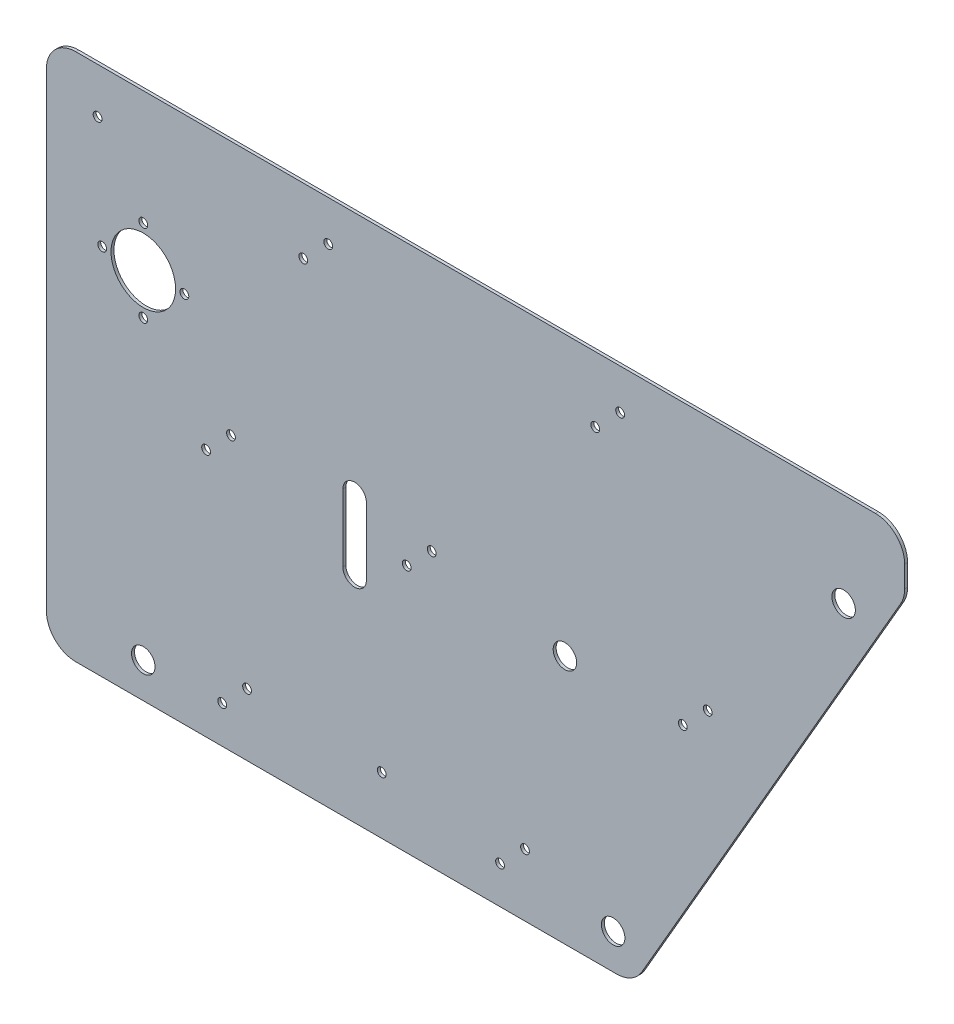
SolidWorks part; units mm, degrees
ref_plane "Front Plane" through (0, 0, 0) normal (0, 0, 1) x (1, 0, 0)
ref_plane "Top Plane" through (0, 0, 0) normal (0, 1, 0) x (1, 0, 0)
ref_plane "Right Plane" through (0, 0, 0) normal (1, 0, 0) x (0, 0, -1)
sketch "Sketch1" plane through (0, 0, 0) normal (0, 0, 1) x (1, 0, 0)
  line L0 (100, 80) -> (192.376, 80)
  line L1 (-100, -80) -> (100, -80)
  line L2 (-100, -80) -> (-100, 80)
  line L3 (-100, 80) -> (100, 80)
  line L4 (100, -80) -> (100, 80)
  line L5 (-100, -80) -> (100, 80) construction
  line L6 (-100, 80) -> (100, -80) construction
  line L7 (192.376, 80) -> (100, -80)
  line L8 (100, 80) -> (100, -80)
  line L10 (-100, 80) -> (192.376, 80)
  line L11 (-100, 80) -> (-100, 100)
  line L12 (-100, 100) -> (192.376, 100)
  line L13 (192.376, 80) -> (192.376, 100)
  point P0 (0, 0)
  dimension "D1" = 160
  dimension "D2" = 200
  dimension "D3" = 30
  dimension "D4" = 20
extrude "Boss-Extrude1" add sketch "Sketch1" along normal blind 1 contours L1 L4 L3 L2 | L7 L0 L4 | L11 L10 L13 L12 region at (0, 0, 0) region at (130.792, 26.6667, 0)
fillet "Fillet1" radius 10 5 edges at (100, -80, 0.5) (-100, -80, 0.5) (192.376, 100, 0.5) (192.376, 80, 0.5) (-100, 100, 0.5)
sketch "Sketch2" plane through (0, 0, 1) normal (0, 0, 1) x (1, 0, 0)
  line L0 (-90, -80) -> (94.2265, -80) construction
  line L1 (191.0363, 77.6795) -> (102.8868, -75) construction
  line L2 (0, -0.55) -> (0, 0.55) construction
  line L3 (-100, -70) -> (-100, 90) construction
  line L4 (5, -6.5) -> (5, 16.5) construction
  line L5 (1, -6.5) -> (1, 16.5)
  line L6 (9, -6.5) -> (9, 16.5)
  line L7 (-90, 100) -> (182.376, 100) construction
  circle A0 centre (93.0718, -68) radius 4
  circle A1 centre (171.5914, 68) radius 4
  circle A2 centre (-67, 47) radius 11
  circle A3 centre (-67, -68) radius 4
  circle A4 centre (-53, 47) radius 1.5
  circle A5 centre (-67, 61) radius 1.5
  circle A6 centre (-81, 47) radius 1.5
  circle A7 centre (-67, 33) radius 1.5
  arc A8 (1, -6.5) -> (9, -6.5) centre (5, -6.5) ccw
  arc A9 (9, 16.5) -> (1, 16.5) centre (5, 16.5) ccw
  circle A10 centre (76.6405, 5) radius 4
  circle A11 centre (54.5495, -67.2426) radius 1.5
  circle A12 centre (63.0348, -58.7574) radius 1.5
  circle A13 centre (14.2259, -60.5) radius 1.5
  circle A14 centre (-40.1271, -67.2426) radius 1.5
  circle A15 centre (-31.6419, -58.7574) radius 1.5
  circle A16 centre (-82.5763, 84.5) radius 1.5
  circle A17 centre (-12.4828, 77.7574) radius 1.5
  circle A18 centre (-3.9975, 86.2426) radius 1.5
  circle A19 centre (86.9654, 77.7574) radius 1.5
  circle A20 centre (95.4507, 86.2426) radius 1.5
  circle A21 centre (22.7626, 4.7574) radius 1.5
  circle A22 centre (31.2479, 13.2426) radius 1.5
  circle A23 centre (-45.6014, 4.7574) radius 1.5
  circle A24 centre (-37.1161, 13.2426) radius 1.5
  circle A25 centre (116.8113, 4.7574) radius 1.5
  circle A26 centre (125.2966, 13.2426) radius 1.5
  point P24 (5, 5)
  point P33 (3.6167, 4.7574)
  point P83 (76.6405, -5)
  dimension "D3" = 8
  dimension "D4" = 8
  dimension "D9" = 22
  dimension "D10" = 8
  dimension "D12" = 3
  dimension "D13" = 3
  dimension "D14" = 3
  dimension "D15" = 3
  dimension "D16" = 14
  dimension "D20" = 4
  dimension "D22" = 8
  dimension "D25" = 3
  dimension "D26" = 3
  dimension "D1" = 12
  dimension "D2" = 12
  dimension "D5" = 32
  dimension "D6" = 12
  dimension "D7" = 53
  dimension "D8" = 33
  dimension "D11" = 12
  dimension "D17" = 14
  dimension "D18" = 14
  dimension "D19" = 14
  dimension "D21" = 23
  dimension "D23" = 95
  dimension "D24" = 95
  dimension "D27" = 5
extrude "Cut-Extrude1" cut sketch "Sketch2" against normal blind 3
